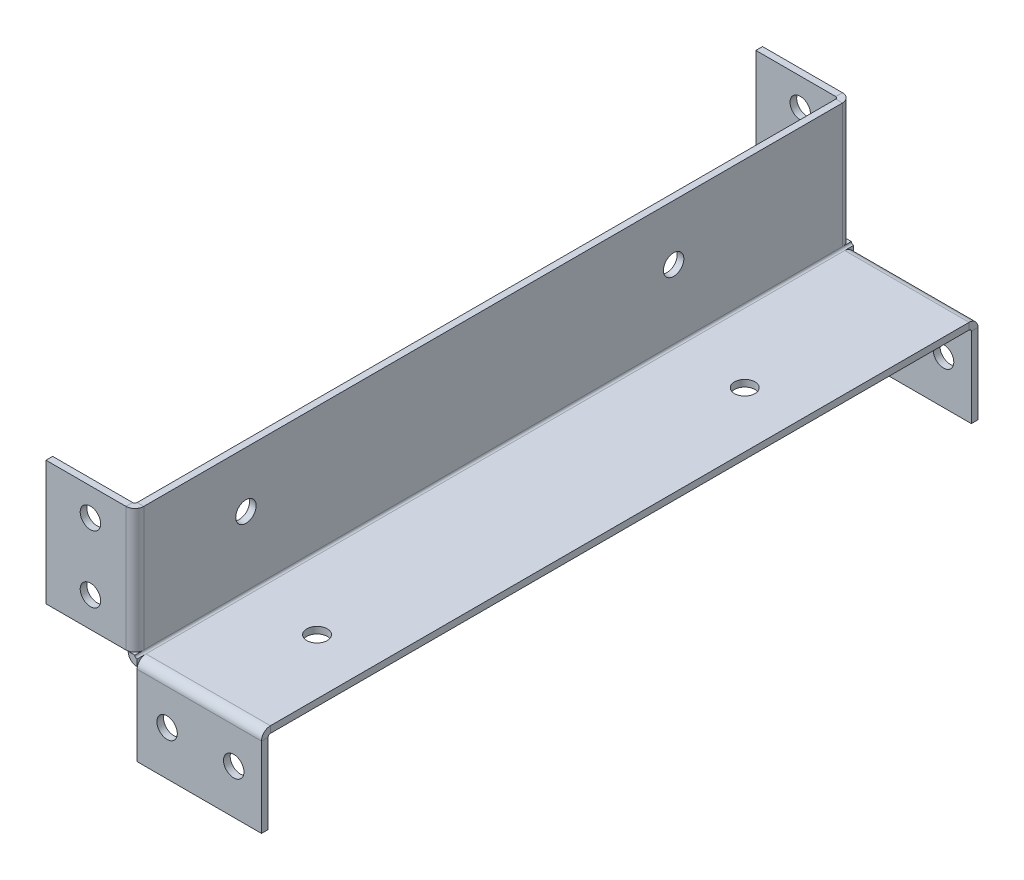
SolidWorks part; units mm, degrees
note: The reader was unsure of these and kept them because the rebuilt part matched: flange length of "Edge-Flange1", "Edge-Flange2".
ref_plane "Front Plane" through (0, 0, 0) normal (0, 0, 1) x (1, 0, 0)
ref_plane "Top Plane" through (0, 0, 0) normal (0, 1, 0) x (1, 0, 0)
ref_plane "Right Plane" through (0, 0, 0) normal (1, 0, 0) x (0, 0, -1)
sketch "Sketch1" plane through (0, 0, 0) normal (0, 1, 0) x (1, 0, 0)
  line L1 (30, 161.25) -> (-30, 161.25)
  line L2 (30, 161.25) -> (30, -161.25)
  line L3 (30, -161.25) -> (-30, -161.25)
  line L4 (-30, 161.25) -> (-30, -161.25)
  line L5 (30, 161.25) -> (-30, -161.25) construction
  line L6 (30, -161.25) -> (-30, 161.25) construction
  point P0 (0, 0)
  dimension "D1" = 60
  dimension "D2" = 322.5
sheet metal parameters "Sheet-Metal1" thickness 3 parameters "D1"=1
base flange "Base-Flange1" sketch "Sketch1" thickness 3 reverse thickness direction yes parameters "D1"=1
edge flange "Edge-Flange1" sketch "Sketch5" flange angle 90 flange length 60 flange position material inside bend radius 1 thickness 3 parameters "D6"=10
sketch "Sketch5" plane through (-30, 3, 0) normal (-1, 0, 0) x (0, 0, 1)
  line L2 (-161.25, 0) -> (-161.25, 57)
  line L3 (-161.25, 57) -> (161.25, 57)
  line L4 (161.25, 57) -> (161.25, 0)
  line L5 (-161.25, 0) -> (161.25, 0) construction
  line L6 (-161.25, 0) -> (161.25, 0)
bend "EdgeBend1" bend radius 1 bend angle 90 parameters "D5"=1
edge flange "Edge-Flange2" sketch "Sketch14" flange profiles "Sketch14", "Sketch15", "Sketch16", "Sketch17" flange angle 90 flange length 40 flange position material inside bend radius 1 thickness 3 relief none parameters "D6"=10, "D8"=0.5
sketch "Sketch14" plane through (-30, 0, 161.25) normal (0, 0, -1) x (0, -1, 0)
  line L1 (-4, 0) -> (-60, 0) construction
  line L2 (-60, 0) -> (-60, 37)
  line L3 (-60, 37) -> (-4, 37)
  line L4 (-4, 37) -> (-4, 0)
  line L5 (-4, 0) -> (-60, 0)
sketch "Sketch15" plane through (0, 0, 161.25) normal (0, 0, -1) x (1, 0, 0)
  line L0 (30, 0) -> (-26, 0) construction
  line L1 (30, 0) -> (-26, 0)
  line L2 (30, 0) -> (30, 37)
  line L3 (30, 37) -> (-26, 37)
  line L4 (-26, 37) -> (-26, 0)
sketch "Sketch16" plane through (-30, 0, -161.25) normal (0, 0, 1) x (0, 1, 0)
  line L0 (60, 0) -> (4, 0) construction
  line L1 (60, 0) -> (4, 0)
  line L2 (60, 0) -> (60, 37)
  line L3 (60, 37) -> (4, 37)
  line L4 (4, 37) -> (4, 0)
sketch "Sketch17" plane through (0, 0, -161.25) normal (0, 0, 1) x (-1, 0, 0)
  line L0 (26, 0) -> (-30, 0) construction
  line L1 (26, 0) -> (-30, 0)
  line L2 (26, 0) -> (26, 37)
  line L3 (26, 37) -> (-30, 37)
  line L4 (-30, 37) -> (-30, 0)
bend "EdgeBend2" bend radius 1 bend angle 90 parameters "D5"=2
bend "EdgeBend3" bend radius 1 bend angle 90 parameters "D5"=3
bend "EdgeBend4" bend radius 1 bend angle 90 parameters "D5"=4
bend "EdgeBend5" bend radius 1 bend angle 90 parameters "D5"=5
sketch "Sketch18" plane through (0, 0, 161.25) normal (0, 0, 1) x (1, 0, 0)
  line L0 (-26, 3) -> (30, 3) construction
  line L1 (-27, 60) -> (-27, 4) construction
  line L2 (-67, 60) -> (-31, 60) construction
  line L3 (30, -1) -> (30, -37) construction
  circle A0 centre (-47, 47.5) radius 4.6
  circle A1 centre (-47, 17.5) radius 4.6
  circle A2 centre (-12.5, -17) radius 4.6
  circle A3 centre (17.5, -17) radius 4.6
  dimension "D7" = 9.2
  dimension "D1" = 30
  dimension "D2" = 30
  dimension "D3" = 20
  dimension "D4" = 20
  dimension "D5" = 12.5
  dimension "D6" = 12.5
extrude "Extrude1" cut sketch "Sketch18" against normal through all normal cut yes
sketch "Sketch19" plane through (-27, 0, 0) normal (1, 0, 0) x (0, 0, -1)
  line L0 (-157.25, 60) -> (157.25, 60) construction
  line L1 (-161.25, 4) -> (-161.25, 60) construction
  line L2 (161.25, 4) -> (161.25, 60) construction
  circle A0 centre (-111.25, 35) radius 4.6
  circle A1 centre (81.25, 35) radius 4.6
  dimension "D4" = 9.2
  dimension "D2" = 80
  dimension "D3" = 50
  dimension "D1" = 25
extrude "Extrude2" cut sketch "Sketch19" against normal blind 3 normal cut yes
sketch "Sketch20" plane through (0, 3, 0) normal (0, 1, 0) x (1, 0, 0)
  line L0 (30, -157.25) -> (30, 157.25) construction
  line L1 (-26, -161.25) -> (30, -161.25) construction
  line L2 (30, 161.25) -> (-26, 161.25) construction
  circle A0 centre (5, 81.25) radius 4.6
  circle A1 centre (5, -111.25) radius 4.6
  dimension "D2" = 9.2
  dimension "D4" = 80
  dimension "D3" = 50
  dimension "D1" = 25
extrude "Extrude3" cut sketch "Sketch20" against normal blind 3 normal cut yes
flat pattern "Flat-Pattern1" [suppressed]
sketch "Bend-Lines1" plane through (0, 4, 0) normal (0, 1, 0) x (-1, 0, 0)
  line L0 (25, -126.4012) -> (-30, -126.4012) construction
  line L1 (82.8023, -126.4012) -> (27.8023, -126.4012) construction
  line L2 (-30, 126.4012) -> (25, 126.4012) construction
  line L3 (27.8023, 126.4012) -> (82.8023, 126.4012) construction
  line L4 (26.4012, -130) -> (26.4012, 130) construction
  line L5 (25, -126.4012) -> (-30, -126.4012) construction
  line L6 (82.8023, -126.4012) -> (27.8023, -126.4012) construction
  line L7 (-30, 126.4012) -> (25, 126.4012) construction
  line L8 (27.8023, 126.4012) -> (82.8023, 126.4012) construction
  line L9 (26.4012, -130) -> (26.4012, 130) construction
bend of the flat pattern "Flatten-<EdgeBend1>1"
bend of the flat pattern "Flatten-<EdgeBend2>1"
bend of the flat pattern "Flatten-<EdgeBend3>1"
bend of the flat pattern "Flatten-<EdgeBend4>1"
bend of the flat pattern "Flatten-<EdgeBend5>1"
